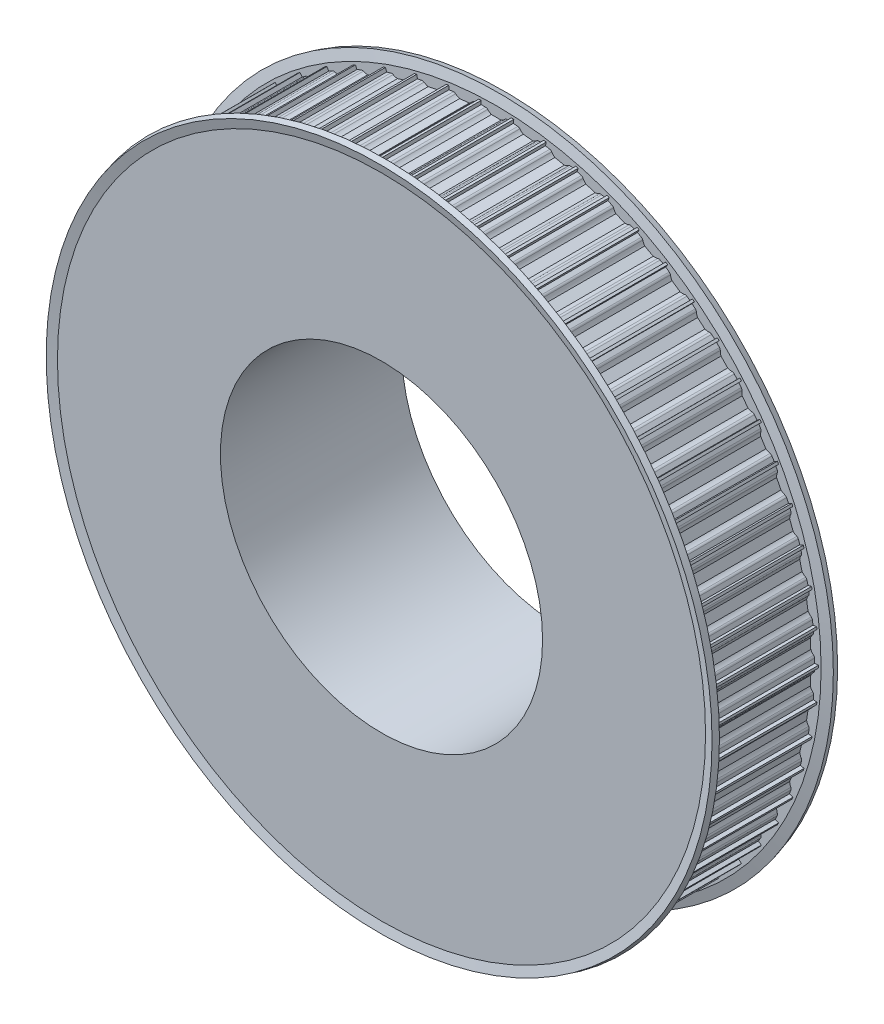
SolidWorks part; units mm, degrees
ref_plane "Front Plane" through (0, 0, 0) normal (0, 0, 1) x (1, 0, 0)
ref_plane "Top Plane" through (0, 0, 0) normal (0, 1, 0) x (1, 0, 0)
ref_plane "Right Plane" through (0, 0, 0) normal (1, 0, 0) x (0, 0, -1)
ref_axis "Axis1" through (0, 0, 55) along (0, 0, -1)
sketch "Sketch1" plane through (0, 0, 0) normal (1, 0, 0) x (0, 0, -1)
  line L0 (0, 40) -> (0, 80)
  line L1 (0, 80) -> (30, 80)
  line L2 (30, 80) -> (30, 55.5)
  line L3 (30, 55.5) -> (45, 55.5)
  line L4 (45, 55.5) -> (45, 40)
  line L5 (45, 40) -> (0, 40)
  dimension "D1" = 40
  dimension "D2" = 40
  dimension "D3" = 30
  dimension "D4" = 15
  dimension "D5" = 15.5
revolve "Revolve1" add sketch "Sketch1" angle 360 about axis through (0, 0, 55) along (0, 0, -1)
sketch "Sketch2" plane through (0, 0, 0) normal (0, 0, 1) x (1, 0, 0)
  line L0 (2.6649, 79) -> (3.75, 79)
  line L1 (-3.75, 81) -> (3.75, 81)
  line L2 (-3.75, 81) -> (-3.75, 79)
  line L3 (-3.75, 79) -> (-2.6649, 79)
  line L4 (3.75, 81) -> (3.75, 79)
  line L5 (1.199, 78.1383) -> (-1.199, 78.1383)
  arc A0 (2.1319, 78.7777) -> (1.199, 78.1383) centre (0, 80.8883) cw
  arc A1 (2.1319, 78.7777) -> (2.6649, 79) centre (2.6649, 78.25) cw
  arc A2 (-2.1319, 78.7777) -> (-2.6649, 79) centre (-2.6649, 78.25) ccw
  arc A3 (-1.199, 78.1383) -> (-2.1319, 78.7777) centre (0, 80.8883) cw
  point P11 (2.3312, 79)
  point P14 (-2.3312, 79)
  dimension "D1" = 3
  dimension "D5" = 0.75
  dimension "D2" = 2
  dimension "D3" = 7.5
  dimension "D4" = 79
  dimension "D6" = 2.75
extrude "Cut-Extrude1" cut sketch "Sketch2" against normal through all
pattern_circular "CirPattern1" count 62 over 360 about axis through (0, 0, 55) along (0, 0, -1) of "Cut-Extrude1"
sketch "Sketch3" plane through (0, 0, 0) normal (1, 0, 0) x (0, 0, -1)
  line L0 (0, 78.5892) -> (0, 77.8587) construction
  line L1 (0, 75.6649) -> (1.5, 75.6649)
  line L2 (0, 75.6649) -> (0, 80.6649)
  line L3 (0, 80.6649) -> (1.5, 80.6649)
  line L4 (1.5, 75.6649) -> (1.5, 80.6649)
  line L5 (1.5, 80.6649) -> (0.0511, 80.2766) construction
  line L6 (1.5, 80.6649) -> (0.8569, 83.0649)
  line L7 (0.0511, 80.2766) -> (-0.592, 82.6766)
  line L8 (0.8569, 83.0649) -> (-0.592, 82.6766)
  line L9 (15, 79.8814) -> (15, -33.4204) construction
  line L10 (0, 79.8814) -> (30, 79.8814) construction
  line L11 (28.5, 80.6649) -> (29.9489, 80.2766) construction
  line L12 (29.1431, 83.0649) -> (30.592, 82.6766)
  line L13 (29.9489, 80.2766) -> (30.592, 82.6766)
  line L14 (28.5, 80.6649) -> (29.1431, 83.0649)
  line L15 (28.5, 75.6649) -> (28.5, 80.6649)
  line L16 (30, 80.6649) -> (28.5, 80.6649)
  line L17 (30, 75.6649) -> (30, 80.6649)
  line L18 (30, 75.6649) -> (28.5, 75.6649)
  point P20 (30, 80.3901)
  dimension "D1" = 1.5
  dimension "D2" = 5
  dimension "D3" = 1.5
  dimension "D4" = 2.4
  dimension "D5" = 165
revolve "Revolve2" add sketch "Sketch3" angle 360 about axis through (0, 0, 55) along (0, 0, -1) region at (0, 78.1649, -0.75) region at (0, 81.7689, -0.4493) region at (0, 81.7689, -29.5507) region at (0, 78.1649, -29.25)
